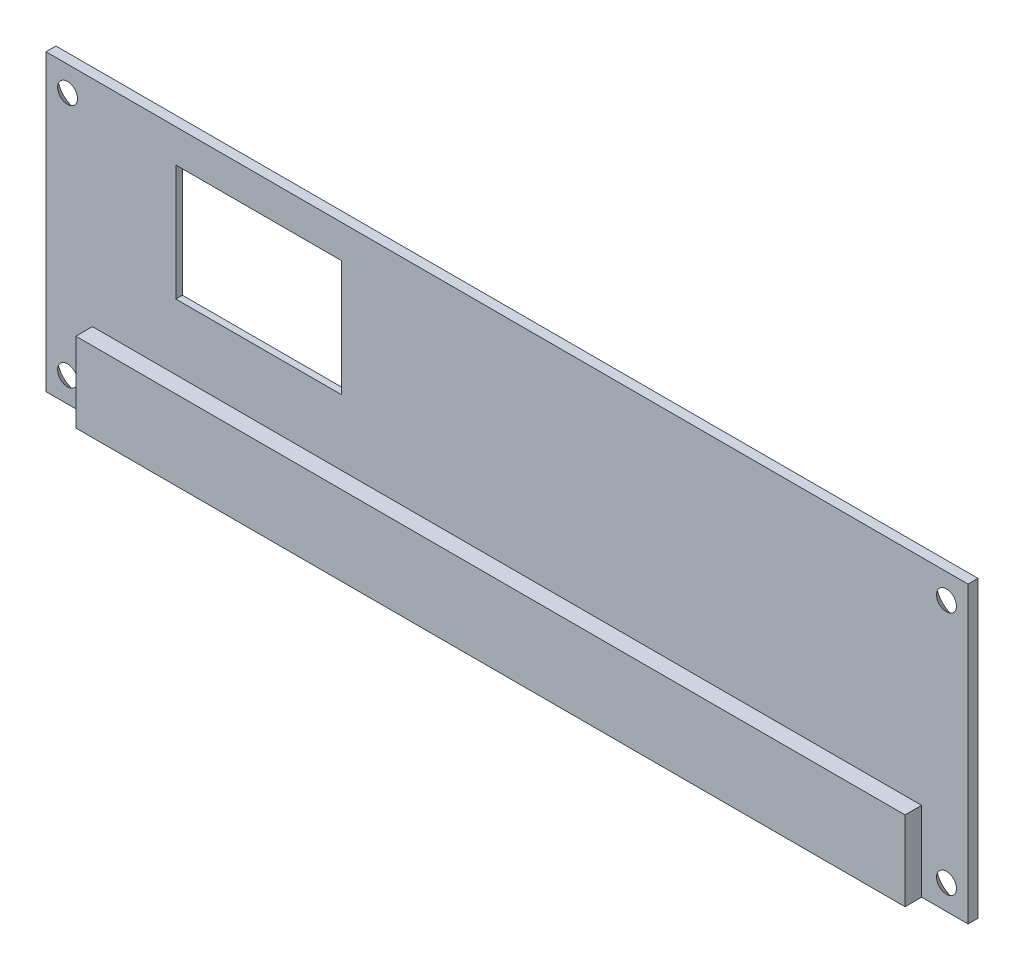
SolidWorks part; units mm, degrees
ref_plane "Front Plane" through (0, 0, 0) normal (0, 0, 1) x (1, 0, 0)
ref_plane "Top Plane" through (0, 0, 0) normal (0, 1, 0) x (1, 0, 0)
ref_plane "Right Plane" through (0, 0, 0) normal (1, 0, 0) x (0, 0, -1)
sketch "Sketch1" plane through (0, 0, 0) normal (0, 0, 1) x (1, 0, 0)
  line L1 (-56, -17.75) -> (56, -17.75)
  line L2 (-56, -17.75) -> (-56, 17.75)
  line L3 (-56, 17.75) -> (56, 17.75)
  line L4 (56, -17.75) -> (56, 17.75)
  line L5 (-56, -17.75) -> (56, 17.75) construction
  line L6 (-56, 17.75) -> (56, -17.75) construction
  point P0 (0, 0)
  dimension "D1" = 112
  dimension "D2" = 35.5
extrude "Boss-Extrude1" add sketch "Sketch1" along normal blind 1.2
sketch "Sketch2" plane through (0, 0, 1.2) normal (0, 0, 1) x (1, 0, 0)
  line L0 (0, 17.75) -> (0, -17.75) construction
  line L1 (-56, 17.75) -> (-50, 17.75)
  line L2 (-56, 17.75) -> (-56, 11.75)
  line L3 (-56, 11.75) -> (-50, 11.75)
  line L4 (-50, 17.75) -> (-50, 11.75)
  line L5 (-56, -17.75) -> (-50, -17.75)
  line L6 (-56, -17.75) -> (-56, -11.75)
  line L7 (-56, -11.75) -> (-50, -11.75)
  line L8 (-50, -17.75) -> (-50, -11.75)
  line L9 (56, 17.75) -> (-56, 17.75) construction
  line L10 (-56, -17.75) -> (56, -17.75) construction
  line L11 (50, -17.75) -> (50, -11.75)
  line L12 (56, -11.75) -> (50, -11.75)
  line L13 (56, -17.75) -> (56, -11.75)
  line L14 (56, -17.75) -> (50, -17.75)
  line L15 (50, 17.75) -> (50, 11.75)
  line L16 (56, 11.75) -> (50, 11.75)
  line L17 (56, 17.75) -> (56, 11.75)
  line L18 (56, 17.75) -> (50, 17.75)
  dimension "D1" = 6
extrude "Boss-Extrude2" add sketch "Sketch2" along normal blind 2
sketch "Sketch3" plane through (0, 0, 3.2) normal (0, 0, 1) x (1, 0, 0)
  line L0 (-50, 11.75) -> (-56, 17.75) construction
  line L1 (-50, -11.75) -> (-56, -17.75) construction
  line L2 (50, -11.75) -> (56, -17.75) construction
  line L3 (-56, 0) -> (56, 0) construction
  line L4 (-56, 11.75) -> (-56, -11.75) construction
  line L5 (56, -11.75) -> (56, 11.75) construction
  line L6 (0, 17.75) -> (0, -17.75) construction
  line L7 (50, 17.75) -> (-50, 17.75) construction
  line L8 (-50, -17.75) -> (50, -17.75) construction
  line L9 (50, 11.75) -> (56, 17.75) construction
  circle A0 centre (-53, 14.75) radius 1.1
  circle A1 centre (-53, -14.75) radius 1.1
  circle A2 centre (53, -14.75) radius 1.1
  circle A3 centre (53, 14.75) radius 1.1
  dimension "D1" = 2.2
extrude "Cut-Extrude1" cut sketch "Sketch3" against normal through all
sketch "Sketch5" plane through (0, 0, 0) normal (0, 0, -1) x (-1, 0, 0)
  line L0 (-56, 17.75) -> (56, 17.75) construction
  line L1 (19.95, -0.25) -> (39.95, -0.25)
  line L2 (19.95, -0.25) -> (19.95, 13.75)
  line L3 (19.95, 13.75) -> (39.95, 13.75)
  line L4 (39.95, -0.25) -> (39.95, 13.75)
  line L5 (19.95, -0.25) -> (39.95, 13.75) construction
  line L6 (19.95, 13.75) -> (39.95, -0.25) construction
  line L7 (56, 17.75) -> (56, -17.75) construction
  point P0 (29.95, 6.75)
  dimension "D1" = 20
  dimension "D2" = 14
  dimension "D3" = 4
  dimension "D4" = 16.05
extrude "Cut-Extrude3" cut sketch "Sketch5" against normal through all
chamfer "Chamfer1" distance 0.4 angle 45 4 edges at (-29.95, 13.75, 0) (-19.95, 6.75, 0) (-29.95, -0.25, 0) (-39.95, 6.75, 0)
sketch "Sketch8" plane through (0, 0, 1.2) normal (0, 0, 1) x (1, 0, 0)
  line L0 (-56, -17.75) -> (-50, -17.75) construction
  line L1 (-56, 17.75) -> (-55.6, 17.75)
  line L2 (-56, 17.75) -> (-56, -17.75)
  line L3 (-56, -17.75) -> (-55.6, -17.75)
  line L4 (-55.6, 17.75) -> (-55.6, -17.75)
  line L5 (50, -17.75) -> (56, -17.75) construction
  line L6 (56, 17.75) -> (55.6, 17.75)
  line L7 (56, 17.75) -> (56, -17.75)
  line L8 (56, -17.75) -> (55.6, -17.75)
  line L9 (55.6, 17.75) -> (55.6, -17.75)
  dimension "D1" = 0.4
extrude "Cut-Extrude6" cut sketch "Sketch8" against normal through all both and the other way through all
sketch "Skizze1" plane through (0, 0, 1.2) normal (0, 0, 1) x (1, 0, 0)
  line L0 (-50, 11.75) -> (-50, -11.75)
  line L2 (-50, -11.75) -> (-55.6, -11.75)
  line L4 (-55.6, -11.75) -> (-55.6, 11.75)
  line L5 (-55.6, 11.75) -> (-50, 11.75)
  line L6 (50, 11.75) -> (50, -11.75)
  line L7 (55.6, -11.75) -> (50, -11.75) construction
  line L8 (50, -11.75) -> (55.6, -11.75)
  line L11 (55.6, -11.75) -> (55.6, 11.75)
  line L12 (55.6, 11.75) -> (50, 11.75)
  line L14 (-50, -8.1568) -> (50, -8.1568)
  line L15 (-50, -8.1568) -> (-50, -17.75)
  line L16 (-50, -17.75) -> (50, -17.75)
  line L17 (50, -8.1568) -> (50, -17.75)
  point P4 (-12.8979, -11.75)
  line M19 (-50, 11.75) -> (-55.6, 11.75)
  line M20 (-55.6, 11.75) -> (-55.6, -11.75)
  line M21 (-55.6, -11.75) -> (-50, -11.75)
  line M22 (-50, -11.75) -> (-50, -17.75)
  line M23 (-50, -17.75) -> (50, -17.75)
  line M24 (50, -17.75) -> (50, -11.75)
  line M25 (50, -11.75) -> (55.6, -11.75)
  line M26 (55.6, -11.75) -> (55.6, 11.75)
  line M27 (55.6, 11.75) -> (50, 11.75)
extrude "Aufsatz-Linear austragen1" add sketch "Skizze1" along normal up to surface (2 mm away) contours L14 L0 L6 M22 M23 M24 | L0 M19 M20 M21 | L6 M27 M25 M26 region at (-52.8, 0, 1.2) region at (0, -12.9534, 1.2) region at (52.8, 0, 1.2) up to face at (-52.8, 14.75, 3.2)
sketch "Sketch9" plane through (0, 0, 1.2) normal (0, 0, 1) x (1, 0, 0)
  line L1 (-50, 17.75) -> (-55.6, 17.75)
  line L2 (-50, 17.75) -> (-50, -17.75)
  line L3 (-50, -17.75) -> (-55.6, -17.75)
  line L4 (-55.6, 17.75) -> (-55.6, -17.75)
  line L5 (50, 17.75) -> (55.6, 17.75)
  line L6 (50, 17.75) -> (50, -17.75)
  line L7 (50, -17.75) -> (55.6, -17.75)
  line L8 (55.6, 17.75) -> (55.6, -17.75)
extrude "Cut-Extrude7" cut sketch "Sketch9" along normal up to surface (2 mm away) up to face at (0, 2.3983, 3.2)
chamfer "Chamfer2" distance 1.3 angle 45 4 edges at (-51.9, 14.75, 0) (-54.1, -14.75, 0) (54.1, -14.75, 0) (51.9, 14.75, 0)
